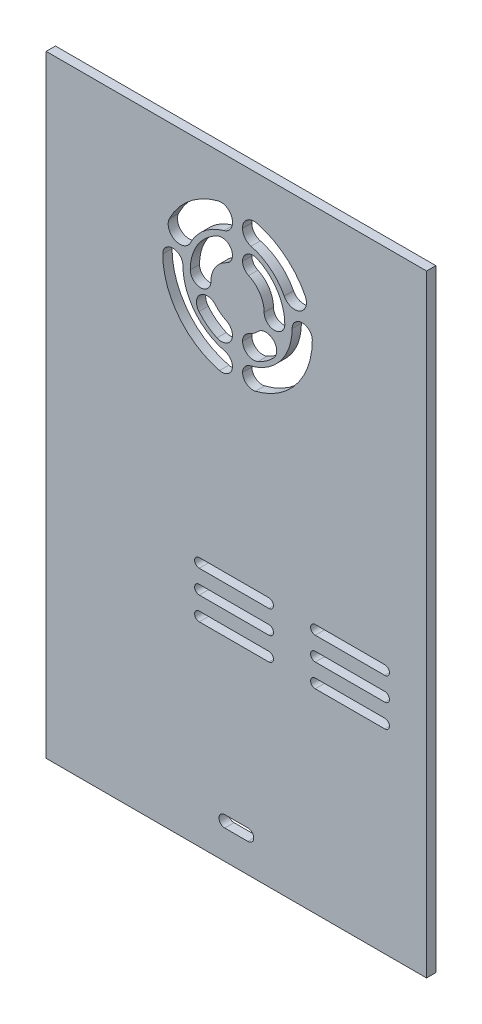
SolidWorks part; units mm, degrees
ref_plane "Front Plane" through (0, 0, 0) normal (0, 0, 1) x (1, 0, 0)
ref_plane "Top Plane" through (0, 0, 0) normal (0, 1, 0) x (1, 0, 0)
ref_plane "Right Plane" through (0, 0, 0) normal (1, 0, 0) x (0, 0, -1)
sketch "Sketch1" plane through (0, 0, 0) normal (0, 0, 1) x (1, 0, 0)
  line L1 (-69.4588, 102.902) -> (94.5412, 102.902)
  line L2 (-69.4588, 102.902) -> (-69.4588, -161.098)
  line L3 (-69.4588, -161.098) -> (94.5412, -161.098)
  line L4 (94.5412, 102.902) -> (94.5412, -161.098)
  dimension "D1" = 164
  dimension "D2" = 264
extrude "Boss-Extrude1" add sketch "Sketch1" along normal blind 4
sketch "Sketch2" plane through (0, 0, 4) normal (0, 0, 1) x (1, 0, 0)
  line L0 (94.5412, 102.902) -> (-69.4588, 102.902) construction
  line L1 (94.5412, -161.098) -> (94.5412, 102.902) construction
  arc A1 (-14.8503, 52.402) -> (40.9326, 52.402) centre (13.0412, 52.402) ccw construction
  arc A6 (-19.1968, 52.402) -> (45.2792, 52.402) centre (13.0412, 52.402) ccw
  arc A11 (-10.5038, 52.402) -> (36.5861, 52.402) centre (13.0412, 52.402) ccw
  arc A12 (-10.5038, 52.402) -> (-19.1968, 52.402) centre (-14.8503, 52.402) ccw
  arc A13 (45.2792, 52.402) -> (36.5861, 52.402) centre (40.9326, 52.402) ccw
  arc A14 (28.9737, 52.402) -> (-2.8914, 52.402) centre (13.0412, 52.402) ccw construction
  arc A15 (33.4266, 52.402) -> (-7.3442, 52.402) centre (13.0412, 52.402) ccw
  arc A16 (24.5208, 52.402) -> (1.5615, 52.402) centre (13.0412, 52.402) ccw
  arc A17 (24.5208, 52.402) -> (33.4266, 52.402) centre (28.9737, 52.402) ccw
  arc A18 (-7.3442, 52.402) -> (1.5615, 52.402) centre (-2.8914, 52.402) ccw
  arc A19 (-11.7928, 64.7794) -> (37.6786, 65.1662) centre (13.0412, 52.402) cw construction
  arc A20 (42.1816, 67.499) -> (-16.3317, 67.0416) centre (13.0412, 52.402) ccw
  arc A21 (33.1757, 62.8333) -> (-7.2539, 62.5172) centre (13.0412, 52.402) ccw
  arc A22 (33.1757, 62.8333) -> (42.1816, 67.499) centre (37.6786, 65.1662) ccw
  arc A23 (-16.3317, 67.0416) -> (-7.2539, 62.5172) centre (-11.7928, 64.7794) ccw
  arc A24 (0, 41.6784) -> (25.255, 40.7448) centre (13.0412, 52.402) ccw construction
  arc A25 (-3.6095, 38.7104) -> (28.6355, 37.5184) centre (13.0412, 52.402) ccw
  arc A26 (3.6095, 44.6464) -> (21.8745, 43.9712) centre (13.0412, 52.402) ccw
  arc A27 (3.6095, 44.6464) -> (-3.6095, 38.7104) centre (0, 41.6784) ccw
  arc A28 (28.6355, 37.5184) -> (21.8745, 43.9712) centre (25.255, 40.7448) ccw
  point P8 (13.0412, 24.5105)
  point P16 (13.0412, 68.3345)
  point P21 (12.8243, 80.1487)
  point P29 (12.4174, 35.5296)
  dimension "D1" = 50.5
  dimension "D2" = 81.5
extrude "Cut-Extrude3" cut sketch "Sketch2" against normal blind 10
sketch "Sketch3" plane through (0, 0, 4) normal (0, 0, 1) x (1, 0, 0)
  line L0 (76.5412, -55.098) -> (46.5412, -55.098) construction
  line L1 (76.5412, -57.098) -> (46.5412, -57.098)
  line L2 (76.5412, -53.098) -> (46.5412, -53.098)
  line L4 (94.5412, 102.902) -> (-69.4588, 102.902) construction
  line L5 (94.5412, -161.098) -> (94.5412, 102.902) construction
  arc A0 (76.5412, -57.098) -> (76.5412, -53.098) centre (76.5412, -55.098) ccw
  arc A1 (46.5412, -53.098) -> (46.5412, -57.098) centre (46.5412, -55.098) ccw
  point P2 (61.5412, -55.098)
  dimension "D1" = 156
  dimension "D2" = 4
  dimension "D3" = 18
  dimension "D4" = 30
extrude "Cut-Extrude4" cut sketch "Sketch3" against normal blind 10
pattern_linear "LPattern1" count 3 spacing 10 along (0, -1, 0) count 2 spacing 50 along (-1, 0, 0) of "Cut-Extrude4"
sketch "Sketch4" plane through (0, 0, 4) normal (0, 0, 1) x (1, 0, 0)
  line L0 (7.5412, -146.098) -> (17.5412, -146.098) construction
  line L1 (7.5412, -143.598) -> (17.5412, -143.598)
  line L2 (7.5412, -148.598) -> (17.5412, -148.598)
  line L3 (-69.4588, 102.902) -> (-69.4588, -161.098) construction
  line L7 (-69.4588, -161.098) -> (94.5412, -161.098) construction
  arc A0 (7.5412, -143.598) -> (7.5412, -148.598) centre (7.5412, -146.098) ccw
  arc A1 (17.5412, -148.598) -> (17.5412, -143.598) centre (17.5412, -146.098) ccw
  point P2 (12.5412, -146.098)
  dimension "D1" = 10
  dimension "D2" = 77
  dimension "D3" = 5
  dimension "D4" = 15
extrude "Cut-Extrude5" cut sketch "Sketch4" against normal blind 10
sketch "Sketch5" plane through (0, 0, 4) normal (0, 0, 1) x (1, 0, 0)
  line L5 (10.8788, 87.0149) -> (15.1979, 87.0149)
  line L6 (10.8788, 87.0149) -> (10.8788, 60.0772)
  line L7 (10.8788, 60.0772) -> (15.1979, 60.0772)
  line L8 (15.1979, 87.0149) -> (15.1979, 60.0772)
  line L9 (10.8788, 42.5734) -> (15.1979, 42.5734)
  line L10 (10.8788, 42.5734) -> (10.8788, 16.8427)
  line L11 (10.8788, 16.8427) -> (15.1979, 16.8427)
  line L12 (15.1979, 42.5734) -> (15.1979, 16.8427)
extrude "Boss-Extrude2" add sketch "Sketch5" against normal blind 4
fillet "Fillet3" radius 5 2 edges at (15.1979, 74.9754, 2) (15.1979, 85.15, 2)
fillet "Fillet4" radius 5 2 edges at (10.8788, 85.1496, 2) (10.8788, 74.9748, 2)
fillet "Fillet5" radius 4.5 2 edges at (10.8788, 63.6761, 2) (10.8788, 72.6724, 2)
fillet "Fillet6" radius 4.5 2 edges at (15.1979, 72.673, 2) (15.1979, 63.6772, 2)
fillet "Fillet7" radius 4.75 2 edges at (15.1979, 30.9532, 2) (15.1979, 40.383, 2)
fillet "Fillet8" radius 4.75 2 edges at (10.8788, 40.384, 2) (10.8788, 30.9537, 2)
fillet "Fillet9" radius 4.5 2 edges at (10.8788, 20.2366, 2) (10.8788, 28.9565, 2)
fillet "Fillet10" radius 4.5 2 edges at (15.1979, 20.2362, 2) (15.1979, 28.956, 2)
